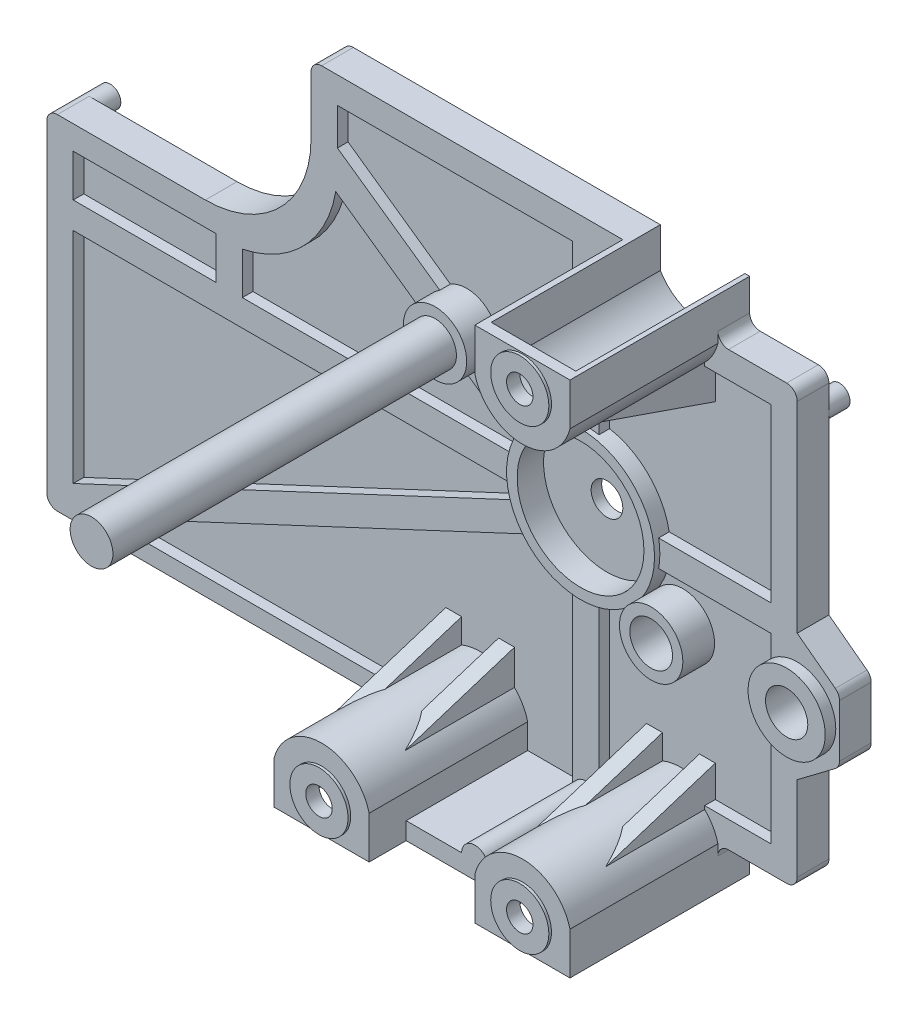
SolidWorks part; units mm, degrees
ref_plane "Alzado" through (0, 0, 0) normal (0, 0, 1) x (1, 0, 0)
ref_plane "Planta" through (0, 0, 0) normal (0, 1, 0) x (1, 0, 0)
ref_plane "Vista lateral" through (0, 0, 0) normal (1, 0, 0) x (0, 0, -1)
sketch "Croquis3" plane through (0, 0, 0) normal (0, 0, 1) x (1, 0, 0)
  line L0 (48.7233, -56.2221) -> (48.7233, -50.2221)
  line L1 (-26.2767, 41.7779) -> (48.7233, 41.7779)
  line L2 (-78.2767, 6.7779) -> (-78.2767, -54.2221)
  line L3 (-76.2767, -56.2221) -> (48.7233, -56.2221)
  line L4 (71.7233, -13.2477) -> (71.7233, -23.1965)
  line L5 (50.7233, -48.2221) -> (61.7233, -48.2221)
  line L6 (63.7233, -46.2221) -> (63.7233, -30.2221)
  line L7 (48.7233, 41.7779) -> (48.7233, 35.7779)
  line L8 (50.7233, 33.7779) -> (61.7233, 33.7779)
  line L9 (63.7233, 31.7779) -> (63.7233, -6.2221)
  line L10 (63.7233, -6.2221) -> (70.9269, -11.6504)
  line L11 (63.7233, -30.2221) -> (70.9269, -24.7938)
  line L12 (-76.2767, 8.7779) -> (-48.2767, 8.7779)
  line L13 (-28.2767, 28.7779) -> (-28.2767, 39.7779)
  arc A0 (-28.2767, 28.7779) -> (-48.2767, 8.7779) centre (-48.2767, 28.7779) cw
  arc A1 (48.7233, 35.7779) -> (50.7233, 33.7779) centre (50.7233, 35.7779) ccw
  arc A2 (48.7233, -50.2221) -> (50.7233, -48.2221) centre (50.7233, -50.2221) cw
  arc A3 (71.7233, -23.1965) -> (70.9269, -24.7938) centre (69.7233, -23.1965) cw
  arc A4 (71.7233, -13.2477) -> (70.9269, -11.6504) centre (69.7233, -13.2477) ccw
  arc A5 (-78.2767, -54.2221) -> (-76.2767, -56.2221) centre (-76.2767, -54.2221) ccw
  arc A6 (-28.2767, 39.7779) -> (-26.2767, 41.7779) centre (-26.2767, 39.7779) cw
  arc A7 (61.7233, 33.7779) -> (63.7233, 31.7779) centre (61.7233, 31.7779) cw
  arc A8 (61.7233, -48.2221) -> (63.7233, -46.2221) centre (61.7233, -46.2221) ccw
  arc A9 (-78.2767, 6.7779) -> (-76.2767, 8.7779) centre (-76.2767, 6.7779) cw
  point P3 (48.7233, 33.7779)
  point P4 (48.7233, -56.2221)
  point P12 (-78.2767, 8.7779)
  point P21 (-28.2767, 8.7779)
  point P24 (48.7233, -48.2221)
  point P35 (63.7233, 33.7779)
  point P38 (63.7233, -48.2221)
  point P41 (-78.2767, 8.7779)
  dimension "D13" = 20
  dimension "D2" = 2
  dimension "D3" = 2
  dimension "D14" = 2
  dimension "D15" = 2
  dimension "D16" = 2
  dimension "D17" = 2
  dimension "D4" = 8
  dimension "D5" = 15
  dimension "D6" = 8
  dimension "D7" = 18
  dimension "D8" = 40
  dimension "D9" = 127
  dimension "D10" = 127
  dimension "D11" = 65
  dimension "D12" = 50
extrude "Saliente-Extruir1" add sketch "Croquis3" along normal mid plane 6
sketch "Croquis4" plane through (0, 0, 3) normal (0, 0, 1) x (1, 0, 0)
  line L0 (48.7233, 41.7779) -> (-26.2767, 41.7779) construction
  line L1 (48.7233, 35.7779) -> (48.7233, 41.7779) construction
  line L2 (30.7233, 41.7779) -> (30.7233, 33.7779)
  line L3 (48.7233, 41.7779) -> (48.7233, 33.7779)
  line L4 (30.7233, 41.7779) -> (48.7233, 41.7779)
  line L5 (39.7233, 41.7779) -> (39.7233, 22.7837) construction
  line L6 (39.7233, 33.7779) -> (48.7233, 33.7779) construction
  line L7 (48.7233, -56.2221) -> (48.7233, -48.2221)
  line L8 (48.7233, -56.2221) -> (30.7233, -56.2221)
  line L9 (-76.2767, -56.2221) -> (48.7233, -56.2221) construction
  line L10 (30.7233, -56.2221) -> (30.7233, -48.2221)
  line L11 (10.7233, -56.2221) -> (10.7233, -48.2221)
  line L12 (-7.2767, -56.2221) -> (-7.2767, -48.2221)
  line L13 (10.7233, -56.2221) -> (-7.2767, -56.2221)
  line L14 (1.7233, -41.2045) -> (39.7233, -41.2045) construction
  arc A0 (30.7233, 33.7779) -> (48.7233, 33.7779) centre (39.7233, 36.0403) ccw
  arc A1 (30.7233, -48.2221) -> (48.7233, -48.2221) centre (39.7233, -50.4845) cw
  arc A2 (-7.2767, -48.2221) -> (10.7233, -48.2221) centre (1.7233, -50.4845) cw
  point P0 (30.7233, 41.7779)
  point P11 (39.7233, 41.7779)
  point P15 (39.7233, 26.7779)
  dimension "D3" = 15
  dimension "D4" = 9.28
  dimension "D8" = 9.28
  dimension "D11" = 9.28
  dimension "D1" = 18
  dimension "D2" = 8
  dimension "D5" = 8
  dimension "D6" = 8
  dimension "D7" = 18
  dimension "D9" = 18
  dimension "D10" = 20
extrude "Saliente-Extruir2" add sketch "Croquis4" along normal blind 28
sketch "Croquis5" plane through (0, 0, 3) normal (0, 0, 1) x (1, 0, 0)
  line L0 (10.7233, -56.2221) -> (10.7233, -52.9396)
  line L1 (10.7233, -56.2221) -> (10.7233, -48.2221) construction
  line L2 (10.7233, -52.9396) -> (21.2233, -52.9396)
  line L3 (30.7233, -48.2221) -> (30.7233, -56.2221) construction
  line L4 (30.7233, -52.9396) -> (30.7233, -56.2221)
  line L5 (30.7233, -56.2221) -> (10.7233, -56.2221)
  line L6 (26.2233, -52.9396) -> (30.7233, -52.9396)
  arc A0 (26.2233, -52.9396) -> (21.2233, -52.9396) centre (23.7233, -52.9396) ccw
  point P10 (23.7233, -52.9396)
  dimension "D1" = 13
extrude "Saliente-Extruir3" add sketch "Croquis5" along normal blind 21
sketch "Croquis7" plane through (0, 0, 3) normal (0, 0, 1) x (1, 0, 0)
  line L0 (-73.2767, -8.7221) -> (-73.2767, -50.1795)
  line L1 (-73.2767, 4.2779) -> (-46.2767, 4.2779)
  line L2 (-73.2767, 4.2779) -> (-73.2767, -3.7221)
  line L3 (-73.2767, -3.7221) -> (-46.2767, -3.7221)
  line L4 (-46.2767, 4.2779) -> (-46.2767, -3.7221)
  line L5 (-78.2767, 6.7779) -> (-78.2767, -54.2221) construction
  line L6 (23.7233, -6.2221) -> (23.7233, 52.9181) construction
  line L7 (-27.068, 3.7779) -> (-41.2767, 3.7779) construction
  line L8 (30.7233, 41.7779) -> (-26.2767, 41.7779) construction
  line L9 (-23.2767, 36.7779) -> (16.7233, 36.7779)
  line L10 (-23.2767, 36.7779) -> (-23.2767, 29.7968)
  line L11 (-41.2767, 4.2325) -> (-41.2767, -3.7221)
  line L12 (-41.2767, -3.7221) -> (4.7234, -3.7221)
  line L13 (4.7234, -3.7221) -> (9.9483, -3.7221)
  line L14 (10.543, -1.5019) -> (-23.5958, 22.5019)
  line L15 (-23.2767, 29.7968) -> (13.8433, 3.6968)
  line L16 (21.2233, 7.5529) -> (21.2233, 36.7779)
  line L17 (21.2233, 36.7779) -> (16.7233, 36.7779)
  line L18 (-28.2767, 39.7779) -> (-28.2767, 28.7779) construction
  line L19 (26.2233, 36.7779) -> (26.2233, 7.5529)
  line L20 (37.4983, -3.7221) -> (58.7233, -3.7221)
  line L21 (58.7233, -3.7221) -> (58.7233, 28.7779)
  line L22 (58.7233, 28.7779) -> (45.5005, 28.7779)
  line L23 (26.2233, 36.7779) -> (30.7233, 36.7779)
  line L24 (30.7233, 41.7779) -> (30.7233, 33.7779) construction
  line L25 (30.7233, 36.7779) -> (30.7233, 33.7779)
  line L27 (61.7233, 33.7779) -> (50.7233, 33.7779) construction
  line L28 (63.7233, -6.2221) -> (63.7233, 31.7779) construction
  line L30 (37.4983, -8.7221) -> (58.7233, -8.7221)
  line L31 (58.7233, -8.7221) -> (58.7233, -43.2221)
  line L32 (58.7233, -43.2221) -> (45.5005, -43.2221)
  line L33 (26.2233, -43.5253) -> (26.2233, -19.9971)
  line L34 (26.2233, -43.5253) -> (26.2233, -52.9396)
  line L35 (26.2233, -52.9396) -> (30.7233, -52.9396)
  line L36 (30.7233, -52.9396) -> (30.7233, -48.2221)
  line L37 (50.7233, -48.2221) -> (61.7233, -48.2221) construction
  line L38 (21.2233, -52.9396) -> (21.2233, -19.9971)
  line L39 (9.9483, -8.7221) -> (-73.2767, -8.7221)
  line L40 (-67.3778, -52.9396) -> (-7.2767, -52.9396)
  line L41 (10.7233, -48.2221) -> (10.7233, -52.9396)
  line L42 (10.7233, -52.9396) -> (21.2233, -52.9396)
  line L43 (-7.2767, -48.2221) -> (-7.2767, -56.2221) construction
  line L44 (-7.2767, -52.9396) -> (-7.2767, -48.2221)
  line L45 (-73.2767, -52.9396) -> (11.6005, -13.2247) construction
  line L46 (-73.2767, -50.1795) -> (10.5483, -10.9569)
  line L48 (13.065, -15.2996) -> (-67.3778, -52.9396)
  arc A0 (-23.5958, 22.5019) -> (-41.2767, 4.2325) centre (-45.7767, 26.2779) cw
  arc A1 (13.065, -15.2996) -> (21.2233, -19.9971) centre (23.7233, -6.2221) ccw
  arc A2 (30.7233, 33.7779) -> (45.5005, 28.7779) centre (39.7233, 36.0403) ccw
  arc A3 (-7.2767, -48.2221) -> (10.7233, -48.2221) centre (1.7233, -50.4845) cw
  arc A4 (30.7233, -48.2221) -> (45.5005, -43.2221) centre (39.7233, -50.4845) cw
  arc A5 (9.9483, -8.7221) -> (10.5483, -10.9569) centre (23.7233, -6.2221) ccw
  arc A6 (10.543, -1.5019) -> (9.9483, -3.7221) centre (23.7233, -6.2221) ccw
  arc A7 (21.2233, 7.5529) -> (13.8433, 3.6968) centre (23.7233, -6.2221) ccw
  arc A8 (37.4983, -3.7221) -> (26.2233, 7.5529) centre (23.7233, -6.2221) ccw
  arc A9 (26.2233, -19.9971) -> (37.4983, -8.7221) centre (23.7233, -6.2221) ccw
  point P4 (-76.2767, 6.7779)
  point P10 (23.7233, -52.9396)
  point P16 (61.2233, 25.7779)
  point P23 (23.7233, -6.2221)
  dimension "D6" = 22.5
  dimension "D10" = 2.5
  dimension "D2" = 5
  dimension "D3" = 8
  dimension "D4" = 27
  dimension "D5" = 40
  dimension "D7" = 48
  dimension "D8" = 5
  dimension "D9" = 5
  dimension "D11" = 8
  dimension "D12" = 5
  dimension "D13" = 5
  dimension "D14" = 5
  dimension "D15" = 2.5
  dimension "D16" = 2.5
  dimension "D17" = 2.5
  dimension "D18" = 2.5
  dimension "D19" = 2.5
  dimension "D20" = 2.5
  dimension "D21" = 5
extrude "Cortar-Extruir1" cut sketch "Croquis7" against normal blind 2
sketch "Croquis8" plane through (0, 0, 3) normal (0, 0, 1) x (1, 0, 0)
  circle A0 centre (23.7233, -6.2221) radius 14
  circle A1 centre (23.7233, -6.2221) radius 12
  point P0 (23.7233, -6.2221)
extrude "Saliente-Extruir4" add sketch "Croquis8" along normal blind 1
sketch "Croquis9" plane through (0, 0, 3) normal (0, 0, 1) x (1, 0, 0)
  circle A0 centre (23.7233, -6.2221) radius 3
  point P0 (23.7233, -6.2221)
  dimension "D1" = 6
extrude "Cortar-Extruir2" cut sketch "Croquis9" against normal blind 37 and the other way blind 39
sketch "Croquis10" plane through (0, 0, 3) normal (0, 0, 1) x (1, 0, 0)
  circle A0 centre (23.7233, -6.2221) radius 12
  circle A1 centre (23.7233, -6.2221) radius 3
extrude "Cortar-Extruir3" cut sketch "Croquis10" against normal blind 4
ref_plane "Plano1" through (-3.2767, 0, 0) normal (-1, 0, 0) x (0, 0, 1)
sketch "Croquis15" plane through (-3.2767, 0, 0) normal (-1, 0, 0) x (0, 0, 1)
  line L1 (3, 6.7779) -> (3, -54.2221) construction
  line L3 (25.08, -44.9368) -> (3, -44.9368)
  line L4 (3, -44.9368) -> (0, -44.9368)
  line L5 (0, -44.9368) -> (0, -36.9368)
  line L6 (0, -36.9368) -> (25.08, -44.9368)
  dimension "D1" = 25.08
  dimension "D2" = 8
extrude "Saliente-Extruir7" add sketch "Croquis15" along normal mid plane 3
ref_plane "Plano2" through (6.7233, 0, 0) normal (1, 0, 0) x (0, 0, -1)
sketch "Croquis17" plane through (6.7233, 0, 0) normal (1, 0, 0) x (0, 0, -1)
  line L3 (-1, -43.8612) -> (-1, -37.2558)
  line L4 (-21.7077, -43.8612) -> (-1, -43.8612)
  line L5 (-1, -37.2558) -> (-21.7077, -43.8612)
  line L6 (-1, -43.8612) -> (-1, -37.2558)
  line L7 (-21.7077, -43.8612) -> (-1, -43.8612)
  line L8 (-1, -37.2558) -> (-21.7077, -43.8612)
  dimension "D1" = 0
extrude "Saliente-Extruir8" add sketch "Croquis17" along normal mid plane 3
ref_plane "Plano3" through (34.7233, 0, 0) normal (-1, 0, 0) x (0, 0, 1)
sketch "Croquis18" plane through (34.7233, 0, 0) normal (-1, 0, 0) x (0, 0, 1)
  line L3 (1, -37.2558) -> (1, -43.8612)
  line L4 (1, -43.8612) -> (21.7077, -43.8612)
  line L5 (21.7077, -43.8612) -> (1, -37.2558)
  line L6 (1, -37.2558) -> (1, -43.8612)
  line L7 (1, -43.8612) -> (21.7077, -43.8612)
  line L8 (21.7077, -43.8612) -> (1, -37.2558)
  dimension "D1" = 0
extrude "Saliente-Extruir9" add sketch "Croquis18" along normal mid plane 3
ref_plane "Plano4" through (44.7233, 0, 0) normal (1, 0, 0) x (0, 0, -1)
sketch "Croquis19" plane through (44.7233, 0, 0) normal (1, 0, 0) x (0, 0, -1)
  line L3 (-1, -43.8612) -> (-1, -37.2558)
  line L4 (-21.7077, -43.8612) -> (-1, -43.8612)
  line L5 (-1, -37.2558) -> (-21.7077, -43.8612)
  line L6 (-1, -43.8612) -> (-1, -37.2558)
  line L7 (-21.7077, -43.8612) -> (-1, -43.8612)
  line L8 (-1, -37.2558) -> (-21.7077, -43.8612)
  dimension "D1" = 0
extrude "Saliente-Extruir10" add sketch "Croquis19" along normal mid plane 3
ref_plane "Plano5" through (34.7233, 0, 0) normal (-1, 0, 0) x (0, 0, 1)
sketch "Croquis20" plane through (34.7233, 0, 0) normal (-1, 0, 0) x (0, 0, 1)
  line L0 (0, 29.8343) -> (0, 21.6278)
  line L1 (0, 21.6278) -> (23.6809, 29.8343)
  line L2 (23.6809, 29.8343) -> (0, 29.8343)
extrude "Saliente-Extruir11" add sketch "Croquis20" along normal mid plane 3
ref_plane "Plano6" through (44.7233, 0, 0) normal (1, 0, 0) x (0, 0, -1)
sketch "Croquis21" plane through (44.7233, 0, 0) normal (1, 0, 0) x (0, 0, -1)
  line L3 (-1, 29.417) -> (-22.4768, 29.417)
  line L4 (-1, 21.9743) -> (-1, 29.417)
  line L5 (-22.4768, 29.417) -> (-1, 21.9743)
  line L6 (-1, 29.417) -> (-22.4768, 29.417)
  line L7 (-1, 21.9743) -> (-1, 29.417)
  line L8 (-22.4768, 29.417) -> (-1, 21.9743)
  dimension "D1" = 0
extrude "Saliente-Extruir12" add sketch "Croquis21" along normal mid plane 3
sketch "Croquis22" plane through (0, 0, 1) normal (0, 0, 1) x (1, 0, 0)
  line L0 (-22.9723, 26.6107) -> (55.2355, -28.3791) construction
  line L1 (-23.2767, 29.7968) -> (13.8433, 3.6968) construction
  circle A0 centre (40.0839, -17.7256) radius 6
  circle A1 centre (-0.8176, 11.0332) radius 6
  circle A2 centre (-0.8176, 11.0332) radius 4.05
  circle A3 centre (40.0839, -17.7256) radius 4.05
  point P0 (23.7233, -6.2221)
  point P6 (40.0839, -17.7256)
  point P9 (-0.8176, 11.0332)
  dimension "D1" = 20
  dimension "D2" = 30
extrude "Saliente-Extruir15" add sketch "Croquis22" along normal blind 6 separate body
sketch "Croquis23" plane through (0, 0, 1) normal (0, 0, 1) x (1, 0, 0)
  circle A0 centre (-0.8176, 11.0332) radius 4.05
  circle A1 centre (40.0839, -17.7256) radius 4.05
  point P0 (-0.8176, 11.0332)
extrude "Cortar-Extruir6" cut sketch "Croquis23" against normal blind 17 and the other way blind 22
sketch "Croquis24" plane through (0, 0, 31) normal (0, 0, 1) x (1, 0, 0)
  circle A0 centre (1.7233, -50.4845) radius 5.5
  circle A1 centre (39.7233, -50.4845) radius 5.5
  circle A2 centre (39.7233, 36.0403) radius 5.5
  point P0 (1.7233, -50.4845)
  point P1 (39.7233, -50.4845)
  point P3 (39.7233, 36.0403)
extrude "Saliente-Extruir16" add sketch "Croquis24" along normal blind 0.5
sketch "Croquis25" plane through (0, 0, 31.5) normal (0, 0, 1) x (1, 0, 0)
  circle A0 centre (1.7233, -50.4845) radius 2.5
  circle A1 centre (39.7233, -50.4845) radius 2.5
  circle A2 centre (39.7233, 36.0403) radius 2.5
extrude "Cortar-Extruir7" cut sketch "Croquis25" against normal blind 40.5
ref_plane "Plano7" through (0, -56.2221, 0) normal (0, -1, 0) x (-1, 0, 0)
sketch "Croquis27" plane through (0, -56.2221, 0) normal (0, -1, 0) x (-1, 0, 0)
  line L0 (7.2767, -3) -> (15.2767, -3)
  line L1 (76.2767, -3) -> (7.2767, -3) construction
  line L2 (15.2767, -3) -> (7.2767, -13)
  line L3 (7.2767, -31) -> (7.2767, -3) construction
  line L4 (7.2767, -13) -> (7.2767, -3)
  dimension "D1" = 8
  dimension "D2" = 10
extrude "Saliente-Extruir17" add sketch "Croquis27" against normal up to vertex (3.2824 mm away) up to point (-7.2767, -52.9396, 3)
sketch "Croquis29" plane through (0, 0, -3) normal (0, 0, -1) x (-1, 0, 0)
  line L0 (-47.8578, -56.2221) -> (-47.8578, -48.7221)
  line L1 (-20.9, -56.2221) -> (20.9, -56.2221) construction
  line L3 (-31.8578, -48.7221) -> (-31.8578, -56.2221)
  line L4 (-31.8578, -56.2221) -> (-47.8578, -56.2221)
  arc A0 (-31.8578, -48.7221) -> (-47.8578, -48.7221) centre (-39.8578, -53.4448) ccw
  dimension "D3" = 9.29
  dimension "D1" = 7.5
  dimension "D2" = 16
extrude "Cortar-Extruir8" cut sketch "Croquis29" against normal blind 32
sketch "Croquis30" plane through (0, 0, -3) normal (0, 0, -1) x (-1, 0, 0)
  line L0 (-9.8533, -56.2221) -> (-9.8533, -48.7221)
  line L1 (-20.9, -56.2221) -> (20.9, -56.2221) construction
  line L3 (6.1467, -48.7221) -> (6.1467, -56.2221)
  line L4 (6.1467, -56.2221) -> (-9.8533, -56.2221)
  line L6 (-47.8578, -48.7221) -> (-47.8578, -56.2221) construction
  line L7 (-31.8578, -56.2221) -> (-31.8578, -48.7221) construction
  arc A0 (-9.8533, -48.7221) -> (6.1467, -48.7221) centre (-1.8533, -53.4448) cw
  point P4 (-39.7233, -50.4845)
  point P7 (-1.7233, -50.4845)
  point P12 (-47.8578, -54.1976)
  point P13 (-31.8578, -53.3924)
  dimension "D4" = 9.29
  dimension "D1" = 7.5
  dimension "D2" = 8.13
  dimension "D3" = 16
extrude "Cortar-Extruir9" cut sketch "Croquis30" against normal blind 32
sketch "Croquis31" plane through (0, 0, -3) normal (0, 0, -1) x (-1, 0, 0)
  line L2 (-47.8233, 41.7779) -> (-47.8233, 34.2779)
  line L3 (-48.7233, 41.7779) -> (26.2767, 41.7779) construction
  line L5 (-31.8233, 34.2779) -> (-31.8233, 41.7779)
  line L6 (-31.8233, 41.7779) -> (-47.8233, 41.7779)
  line L7 (-48.7233, 35.7779) -> (-48.7233, 41.7779) construction
  arc A0 (-47.8233, 34.2779) -> (-31.8233, 34.2779) centre (-39.8233, 39.0006) ccw
  dimension "D3" = 0.9
  dimension "D4" = 9.29
  dimension "D1" = 7.5
  dimension "D2" = 16
extrude "Cortar-Extruir10" cut sketch "Croquis31" against normal blind 32
sketch "Croquis32" plane through (0, 0, -3) normal (0, 0, -1) x (-1, 0, 0)
  line L0 (9.1467, -56.2221) -> (9.1467, -51.2221)
  line L1 (-20.9, -56.2221) -> (20.9, -56.2221) construction
  line L2 (15.1467, -48.7221) -> (15.1467, -47.2221)
  line L3 (16.1467, -46.2221) -> (32.1467, -46.2221)
  line L4 (33.1467, -47.2221) -> (33.1467, -48.7221)
  line L5 (34.6467, -50.2221) -> (38.1467, -50.2221)
  line L6 (39.1467, -51.2221) -> (39.1467, -56.2221)
  line L7 (39.1467, -56.2221) -> (9.1467, -56.2221)
  line L8 (10.1467, -50.2221) -> (13.6467, -50.2221)
  line L9 (6.1467, -56.2221) -> (6.1467, -48.7221) construction
  arc A0 (39.1467, -51.2221) -> (38.1467, -50.2221) centre (38.1467, -51.2221) ccw
  arc A1 (10.1467, -50.2221) -> (9.1467, -51.2221) centre (10.1467, -51.2221) ccw
  arc A2 (33.1467, -47.2221) -> (32.1467, -46.2221) centre (32.1467, -47.2221) ccw
  arc A3 (16.1467, -46.2221) -> (15.1467, -47.2221) centre (16.1467, -47.2221) ccw
  arc A4 (33.1467, -48.7221) -> (34.6467, -50.2221) centre (34.6467, -48.7221) ccw
  arc A5 (15.1467, -48.7221) -> (13.6467, -50.2221) centre (13.6467, -48.7221) cw
  point P12 (39.1467, -50.2221)
  point P15 (9.1467, -50.2221)
  point P18 (33.1467, -46.2221)
  point P23 (33.1467, -50.2221)
  point P26 (15.1467, -50.2221)
  dimension "D7" = 1
  dimension "D8" = 1.5
  dimension "D1" = 30
  dimension "D2" = 6
  dimension "D3" = 6
  dimension "D4" = 6
  dimension "D5" = 6
  dimension "D6" = 4
  dimension "D9" = 3
extrude "Saliente-Extruir18" add sketch "Croquis32" along normal blind 4
sketch "Croquis33" plane through (0, 0, -7) normal (0, 0, -1) x (-1, 0, 0)
  line L0 (9.1467, -53.7221) -> (39.1467, -53.7221) construction
  line L1 (9.1467, -51.2221) -> (9.1467, -56.2221) construction
  line L2 (39.1467, -56.2221) -> (39.1467, -51.2221) construction
  line L3 (9.1467, -51.2221) -> (9.1467, -56.2221) construction
  circle A0 centre (11.1467, -53.7221) radius 0.75
  circle A1 centre (37.1467, -53.7221) radius 0.75
  point P6 (11.1467, -53.7221)
  point P7 (37.1467, -53.7221)
  dimension "D3" = 1.5
  dimension "D4" = 1.5
  dimension "D1" = 2
  dimension "D2" = 2
extrude "Cortar-Extruir11" cut sketch "Croquis33" against normal blind 4
sketch "Croquis34" plane through (0, 0, -3) normal (0, 0, -1) x (-1, 0, 0)
  line L0 (74.2767, -54.2221) -> (74.2767, -50.2221)
  line L1 (-61.7233, 31.7779) -> (-61.7233, 14.7845) construction
  line L2 (78.2767, -50.2221) -> (78.2767, -54.2221)
  line L3 (-61.7233, 14.7845) -> (-61.7233, -6.4142) construction
  line L4 (-61.7233, -6.4142) -> (-61.7233, -37.9719) construction
  arc A0 (74.2767, -54.2221) -> (78.2767, -54.2221) centre (76.2767, -54.2221) ccw
  arc A1 (78.2767, -50.2221) -> (74.2767, -50.2221) centre (76.2767, -50.2221) ccw
  circle A2 centre (76.2767, 6.7779) radius 2
  circle A3 centre (-61.7233, 26.7779) radius 2
  circle A4 centre (-61.7233, -26.2221) radius 2
  point P0 (76.2767, -54.2221)
  point P15 (-61.7233, 26.7779)
  point P18 (-61.7233, -26.2221)
  dimension "D1" = 5
  dimension "D2" = 53
extrude "Saliente-Extruir19" add sketch "Croquis34" along normal blind 4
sketch "Croquis35" plane through (0, 0, -7) normal (0, 0, -1) x (-1, 0, 0)
  circle A0 centre (-61.7233, 26.7779) radius 1
  circle A1 centre (-61.7233, -26.2221) radius 1
  circle A2 centre (76.2767, 6.7779) radius 1
  circle A3 centre (76.2767, -54.2221) radius 1
extrude "Cortar-Extruir12" cut sketch "Croquis35" against normal blind 3.5
sketch "Croquis36" plane through (0, 0, -7) normal (0, 0, -1) x (-1, 0, 0)
  circle A0 centre (76.2767, -50.2221) radius 0.8
  point P0 (76.2767, -50.2221)
extrude "Saliente-Extruir20" add sketch "Croquis36" along normal blind 0.2
dome "Cúpula1" faces to dome 1 distance 1 reverse direction no elliptical dome no face at (-77.0767, -50.2221, -7.2) parameters "D1"=1
sketch "Croquis39" plane through (0, 0, 1) normal (0, 0, 1) x (1, 0, 0)
  line L0 (71.7233, -23.1965) -> (71.7233, -13.2477) construction
  line L1 (71.7233, -18.2221) -> (55.9989, -18.2221) construction
  line L2 (63.7233, -6.2221) -> (63.7233, -30.2221) construction
  circle A0 centre (63.7233, -18.2221) radius 7.3
  point P0 (71.7233, -18.2221)
  point P9 (63.7233, -18.2221)
extrude "Saliente-Extruir21" add sketch "Croquis39" along normal blind 4
sketch "Croquis40" plane through (0, 0, 5) normal (0, 0, 1) x (1, 0, 0)
  circle A0 centre (63.7233, -18.2221) radius 4
extrude "Cortar-Extruir13" cut sketch "Croquis40" against normal blind 38 and the other way blind 26
sketch "Croquis42" plane through (0, 0, 7) normal (0, 0, 1) x (1, 0, 0)
  circle A0 centre (-0.8176, 11.0332) radius 4.05
  dimension "D1" = 8.1
extrude "Saliente-Extruir24" add sketch "Croquis42" along normal blind 65
